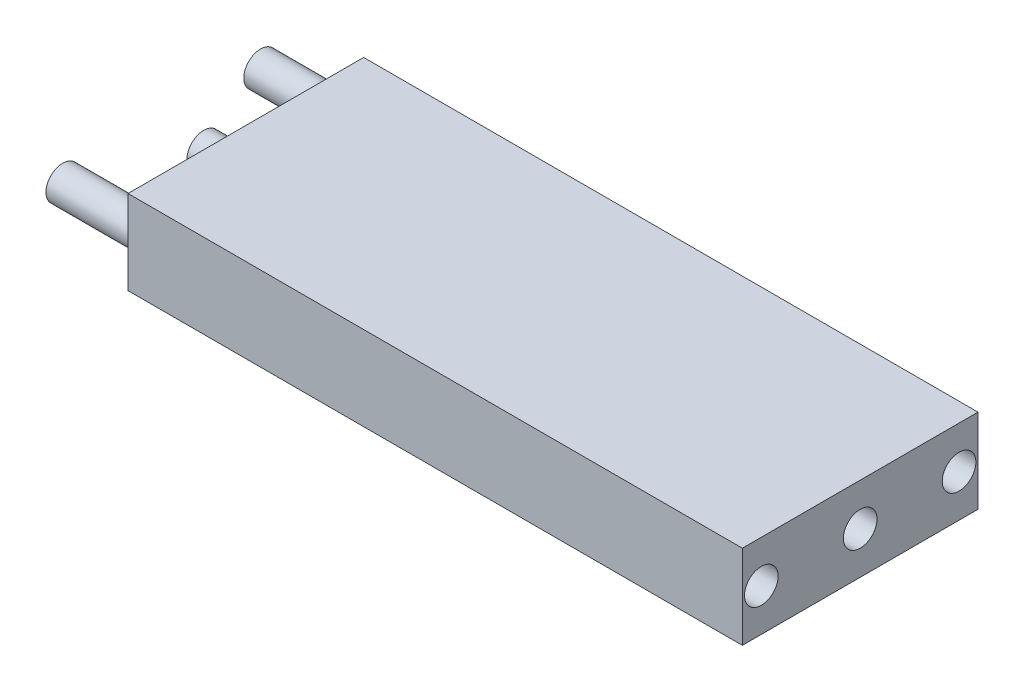
SolidWorks part; units mm, degrees
ref_plane "Front Plane" through (0, 0, 0) normal (0, 0, 1) x (1, 0, 0)
ref_plane "Top Plane" through (0, 0, 0) normal (0, 1, 0) x (1, 0, 0)
ref_plane "Right Plane" through (0, 0, 0) normal (1, 0, 0) x (0, 0, -1)
sketch "Sketch2" plane through (0, 0, 0) normal (0, 1, 0) x (1, 0, 0)
  line L1 (-36.5, -14) -> (36.5, -14)
  line L2 (-36.5, -14) -> (-36.5, 14)
  line L3 (-36.5, 14) -> (36.5, 14)
  line L4 (36.5, -14) -> (36.5, 14)
  line L5 (-36.5, -14) -> (36.5, 14) construction
  line L6 (-36.5, 14) -> (36.5, -14) construction
  point P0 (0, 0)
  dimension "D1" = 28
  dimension "D2" = 73
extrude "Boss-Extrude1" add sketch "Sketch2" along normal mid plane 10
sketch "Sketch3" plane through (0, 0, 0) normal (1, 0, 0) x (0, 0, -1)
  line L0 (-11.75, 0) -> (11.75, 0) construction
  circle A0 centre (0, 0) radius 2
  circle A1 centre (11.75, 0) radius 2
  circle A2 centre (-11.75, 0) radius 2
  point P4 (0, 0)
  dimension "D1" = 4
  dimension "D2" = 4
  dimension "D3" = 4
  dimension "D4" = 23.5
extrude "Cut-Extrude2" cut sketch "Sketch3" against normal blind 5 from surface starting at face at (36.5, 0, 0)
extrude "Boss-Extrude2" add sketch "Sketch3<2>" along normal mid plane 20 from surface contours A1 | A2 starting at face at (-36.5, 0, 0)
sketch "Sketch3<2>" plane through (0, 0, 0) normal (1, 0, 0) x (0, 0, -1) same geometry as "Sketch3"
extrude "Boss-Extrude3" add sketch "Sketch3<3>" along normal mid plane 10 from surface contours A0 starting at face at (-36.5, 0, 9.75)
sketch "Sketch3<3>" plane through (0, 0, 0) normal (1, 0, 0) x (0, 0, -1) same geometry as "Sketch3"
